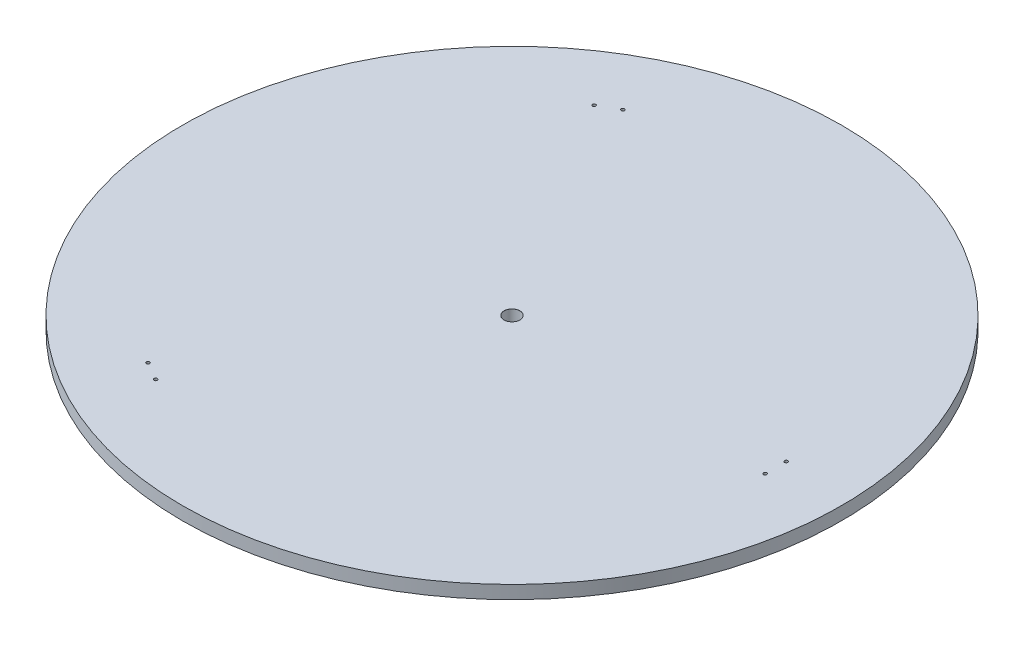
SolidWorks part; units mm, degrees
ref_plane "Plan de face" through (0, 0, 0) normal (0, 0, 1) x (1, 0, 0)
ref_plane "Plan de dessus" through (0, 0, 0) normal (0, 1, 0) x (1, 0, 0)
ref_plane "Plan de droite" through (0, 0, 0) normal (1, 0, 0) x (0, 0, -1)
sketch "Esquisse1" plane through (0, 0, 0) normal (0, 1, 0) x (1, 0, 0)
  circle A0 centre (0, 0) radius 250
  dimension "D1" = 500
extrude "Boss.-Extru.1" add sketch "Esquisse1" along normal mid plane 10
sketch "Esquisse5" plane through (0, 5, 0) normal (0, 1, 0) x (1, 0, 0)
  point P0 (0, 0)
hole_wizard "Dégagement M101" positions "Esquisse5" profile "Esquisse4" hole size "M10" standard "ISO" end condition through all
sketch "Esquisse4" plane through (0, 5, 0) normal (1, 0, 0) x (0, 0, 1)
  line L0 (0, 0) -> (0, 10)
  line L1 (0, 10) -> (6, 10)
  line L2 (6, 10) -> (6, 0.025)
  line L3 (6, 0.025) -> (6.025, 0)
  line L5 (6.025, 0) -> (0, 0)
  line L6 (-6, 0.025) -> (-6.025, 0) construction
  line L11 (0, -6.35) -> (0, 107.95) construction
  dimension "Diamètre du perçage jusqu'au prochain" = 12
  dimension "Profondeur du perçage jusqu'au prochain" = 10
  dimension "Diamètre du fraisage entrant" = 12.05
  dimension "Angle du fraisage entrant" = 90
sketch "Esquisse6" plane through (0, 5, 0) normal (0, 1, 0) x (1, 0, 0)
  line L0 (0, 0) -> (458.2969, 0) construction
  line L1 (0, 0) -> (-167.1022, 289.4294) construction
  line L2 (0, 0) -> (-171.7601, -297.4973) construction
  circle A0 centre (200, 8) radius 1.25
  circle A5 centre (200, -8) radius 1.25
  dimension "D5" = 2.5
  dimension "D3" = 8
  dimension "D4" = 200
  dimension "D1" = 120
  dimension "D2" = 120
extrude "Enlèv. mat.-Extru.1" cut sketch "Esquisse6" against normal through all
pattern_circular "Répétition circulaire1" count 3 over 360 about axis through (0, 5, 0) along (0, 1, 0) of "Enlèv. mat.-Extru.1" reverse direction yes
